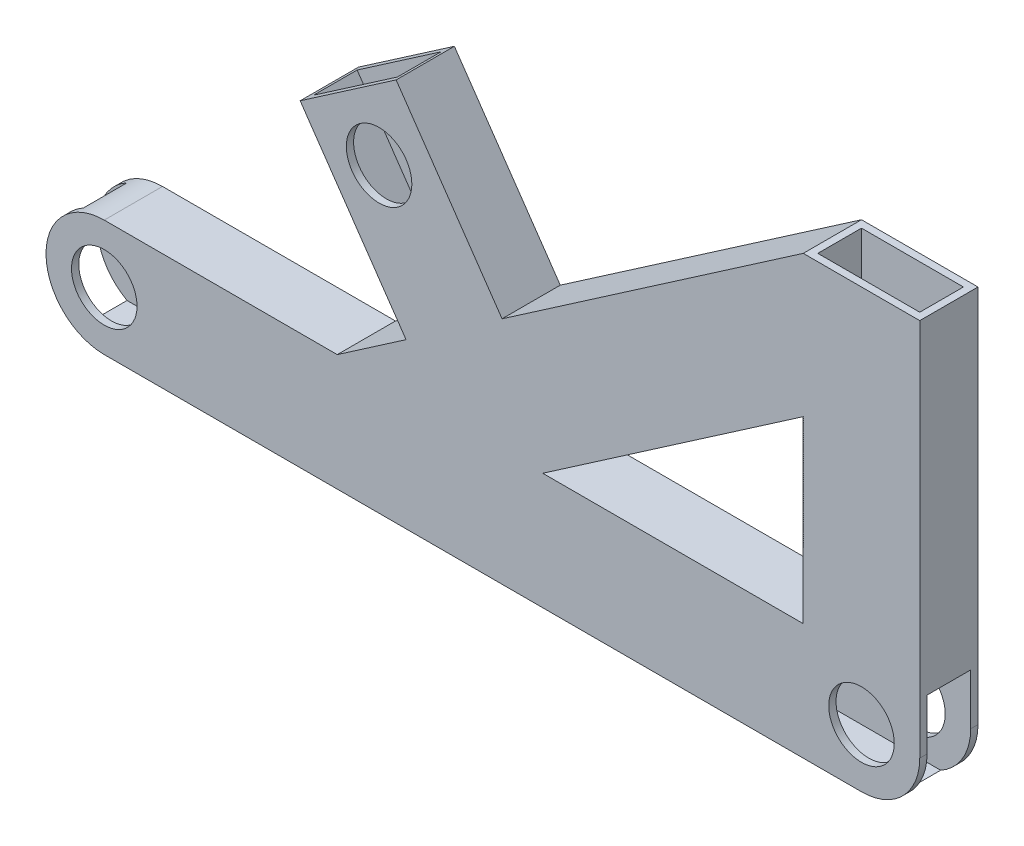
SolidWorks part; units mm, degrees
material "6061 Alloy"
ref_plane "Front Plane" through (0, 0, 0) normal (0, 0, 1) x (1, 0, 0)
ref_plane "Top Plane" through (0, 0, 0) normal (0, 1, 0) x (1, 0, 0)
ref_plane "Right Plane" through (0, 0, 0) normal (1, 0, 0) x (0, 0, -1)
sketch "Sketch1" plane through (0, 0, 0) normal (0, 0, 1) x (1, 0, 0)
  line L0 (-991.9447, 782.203) -> (-1195.1447, 642.3678)
  line L6 (-991.9447, 782.203) -> (-963.1461, 740.3546)
  line L12 (-1322.1447, 642.3678) -> (-941.1447, 642.3678)
  line L13 (-1128.284, 591.5678) -> (-1128.284, 642.3678)
  line L14 (-1322.1447, 642.3678) -> (-1322.1447, 591.5678)
  line L15 (-1195.1447, 642.3678) -> (-1166.3461, 600.5194)
  line L16 (-963.1461, 740.3546) -> (-1166.3461, 600.5194)
  line L17 (-1322.1447, 591.5678) -> (-941.1447, 591.5678)
  line L44 (-941.1447, 642.3678) -> (-941.1447, 591.5678)
  line L45 (-941.1447, 642.3678) -> (-991.9447, 642.3678)
  line L46 (-941.1447, 642.3678) -> (-941.1447, 782.203)
  line L47 (-941.1447, 782.203) -> (-991.9447, 782.203)
  line L48 (-991.9447, 642.3678) -> (-991.9447, 782.203)
  circle A15 centre (-1296.7447, 616.9678) radius 14.2875
  circle A17 centre (-1296.7447, 616.9678) radius 25.4
  circle A18 centre (-1296.7447, 616.9678) radius 38.1
  circle A20 centre (-966.5447, 616.9678) radius 14.2875
  point P1 (0, 0)
  point P5 (-1198.5672, 686.9464)
  point P6 (-1194.7759, 642.3678)
  point P19 (-1322.1447, 616.9678)
  point P20 (-941.1447, 616.9678)
  dimension "D2" = 50.8
  dimension "D3" = 50.8
  dimension "D10" = 25.4
  dimension "D11" = 50.8
  dimension "D12" = 76.2
  dimension "D4" = 25.4
  dimension "D5" = 50.8
  dimension "D6" = 254
  dimension "D7" = 381
extrude "Boss-Extrude3" add sketch "Sketch1" along normal blind 25.4 contours A17 L12 L14 | A17 L14 L17 | L17 A18 L12 A17 | A18 L17 L13 L16 L15 L12 | L16 L13 L12 L15 | L16 L48 L0 L12 | L16 L12 L13 | L44 L12 L16 L13 L17 A20 | L48 L12 L46 L47 L6 L16 | L48 L16 L6 | A20 | A17 A15 | A15 | A17 region at (-1073.2545, 698.3224, 0) region at (-964.2874, 707.2264, 0) region at (-982.3451, 747.698, 0) region at (-1206.9346, 613.449, 0) region at (-1159.3453, 627.5021, 0) region at (-1120.7009, 637.1493, 0) region at (-1270.0443, 616.9678, 0) region at (-1037.9841, 616.5541, 0) region at (-1316.4711, 636.6942, 0) region at (-1279.2921, 634.4203, 0) region at (-1316.4711, 597.2413, 0) region at (-1296.7447, 616.9678, 0) region at (-966.5447, 616.9678, 0)
sketch "Sketch9" plane through (0, 0, 25.4) normal (0, 0, 1) x (1, 0, 0)
  circle A1 centre (-1296.7447, 616.9678) radius 14.2875
  circle A2 centre (-1296.7447, 616.9678) radius 14.2875
  circle A3 centre (-966.5447, 616.9678) radius 14.2875
  circle A4 centre (-966.5447, 616.9678) radius 14.2875
  dimension "D2" = 0
  dimension "D6" = 0
extrude "Cut-Extrude7" cut sketch "Sketch9" against normal through all
sketch "Sketch10" plane through (-1322.1447, 0, 0) normal (-1, 0, 0) x (0, 0, 1)
  line L0 (25.4, 642.3678) -> (0, 642.3678) construction
  line L1 (3.175, 639.1928) -> (22.225, 639.1928)
  line L2 (3.175, 639.1928) -> (3.175, 594.7428)
  line L3 (3.175, 594.7428) -> (22.225, 594.7428)
  line L4 (22.225, 639.1928) -> (22.225, 594.7428)
  line L5 (25.4, 591.5678) -> (0, 591.5678) construction
  line L6 (25.4, 642.3678) -> (25.4, 591.5678) construction
  dimension "D1" = 3.175
  dimension "D2" = 3.175
  dimension "D3" = 3.175
  dimension "D4" = 3.175
extrude "Cut-Extrude8" cut sketch "Sketch10" against normal through all
sketch "Sketch11" plane through (0, 782.203, 0) normal (0, 1, 0) x (1, 0, 0)
  line L0 (-991.9447, -25.4) -> (-991.9447, 0) construction
  line L1 (-988.7697, -3.175) -> (-944.3197, -3.175)
  line L2 (-988.7697, -3.175) -> (-988.7697, -22.225)
  line L3 (-988.7697, -22.225) -> (-944.3197, -22.225)
  line L4 (-944.3197, -3.175) -> (-944.3197, -22.225)
  line L5 (-941.1447, 0) -> (-991.9447, 0) construction
  line L6 (-941.1447, -25.4) -> (-941.1447, 0) construction
  line L7 (-941.1447, -25.4) -> (-991.9447, -25.4) construction
  dimension "D1" = 3.175
  dimension "D2" = 3.175
  dimension "D3" = 3.175
  dimension "D4" = 3.175
extrude "Cut-Extrude9" cut sketch "Sketch11" against normal up to surface (139.8352 mm away) up to face at (-1048.7396, 642.3678, 12.7)
sketch "Sketch13" plane through (0, 0, 0) normal (0, 0, 1) x (1, 0, 0)
  line L0 (-1211.3195, 730.1409) -> (-1165.1308, 663.0223)
  line L1 (-1211.3195, 730.1409) -> (-1169.4712, 758.9395)
  line L2 (-1165.1308, 663.0223) -> (-1123.2825, 691.8208)
  line L3 (-1169.4712, 758.9395) -> (-1123.2825, 691.8208)
  line L4 (-1322.1447, 591.5678) -> (-941.1447, 591.5678) construction
  line L5 (-941.1447, 782.203) -> (-941.1447, 591.5678) construction
  line L12 (-991.9447, 782.203) -> (-1195.1447, 642.3678)
  line L13 (-1195.1447, 642.3678) -> (-1322.1447, 642.3678)
  line L14 (-1322.1447, 642.3678) -> (-1322.1447, 591.5678)
  line L15 (-1322.1447, 591.5678) -> (-941.1447, 591.5678)
  line L16 (-941.1447, 591.5678) -> (-941.1447, 782.203)
  line L17 (-941.1447, 782.203) -> (-991.9447, 782.203)
  circle A0 centre (-1176.9051, 722.9905) radius 14.2875
  circle A1 centre (-1176.9051, 722.9905) radius 38.1
  dimension "D1" = 127
  dimension "D2" = 381
  dimension "D3" = 246.666
  dimension "D4" = 50.8
  dimension "D5" = 190.6352
  dimension "D6" = 50.8
  dimension "D7" = 80.6227
  dimension "D8" = 145.2396
  dimension "D9" = 50.8
  dimension "D10" = 25.4
extrude "Boss-Extrude4" add sketch "Sketch13" along normal blind 25.4 contours L0 A1 L3 L1 A0 | A1 L0 L2 L3 region at (-1189.8108, 743.6907, 0) region at (-1149.996, 686.4501, 0)
sketch "Sketch14" plane through (-730.2692, 1061.183, 0) normal (-0.5669, 0.8238, 0) x (0.8238, 0.5669, 0)
  line L0 (-533.1505, -25.4) -> (-533.1505, 0) construction
  line L1 (-536.3255, -3.175) -> (-580.7755, -3.175)
  line L2 (-536.3255, -3.175) -> (-536.3255, -22.225)
  line L3 (-536.3255, -22.225) -> (-580.7755, -22.225)
  line L4 (-580.7755, -3.175) -> (-580.7755, -22.225)
  line L5 (-583.9505, -25.4) -> (-533.1505, -25.4) construction
  line L6 (-583.9505, -25.4) -> (-583.9505, 0) construction
  line L7 (-583.9505, 0) -> (-533.1505, 0) construction
  dimension "D1" = 3.175
  dimension "D2" = 3.175
  dimension "D3" = 3.175
  dimension "D4" = 3.175
extrude "Cut-Extrude10" cut sketch "Sketch14" against normal up to surface (81.4758 mm away) up to face at (-1057.6136, 737.0119, 12.7)
fillet "Fillet3" radius 25.4 3 edges at (-941.1447, 591.5678, 12.7) (-1322.1447, 591.5678, 12.7) (-1322.1447, 642.3678, 12.7)
